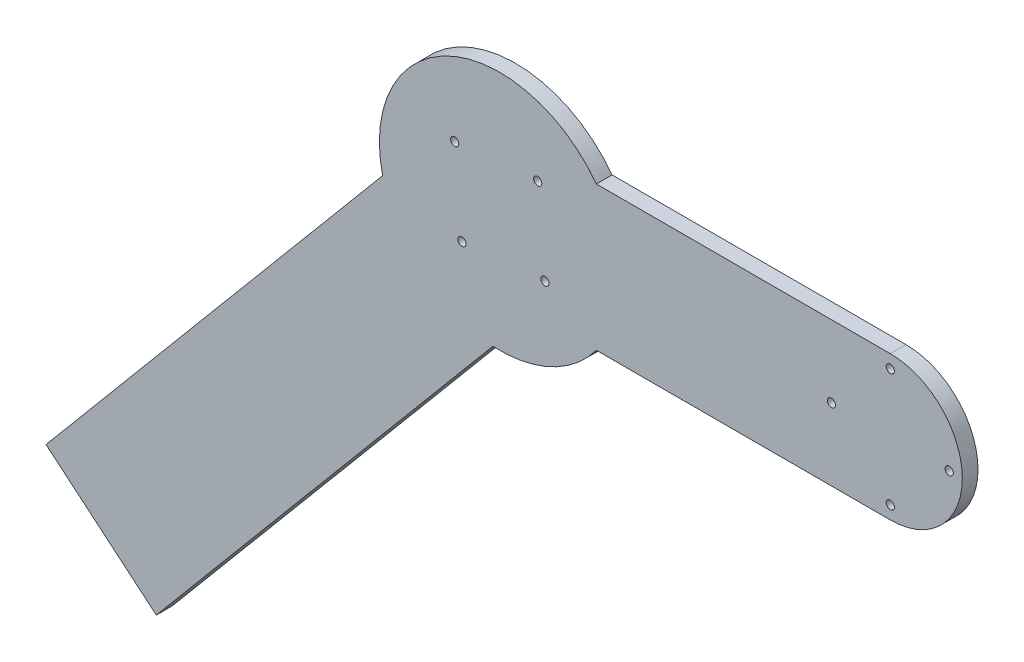
SolidWorks part; units mm, degrees
ref_plane "Front Plane" through (0, 0, 0) normal (0, 0, 1) x (1, 0, 0)
ref_plane "Top Plane" through (0, 0, 0) normal (0, 1, 0) x (1, 0, 0)
ref_plane "Right Plane" through (0, 0, 0) normal (1, 0, 0) x (0, 0, -1)
sketch "Sketch1" plane through (0, 0, 0) normal (0, 1, 0) x (1, 0, 0)
  line L0 (-47.5, -29.9135) -> (47.5, -29.9135) construction
  line L1 (-47.5, 56.6115) -> (47.5, 56.6115) construction
  line L2 (-47.5, 56.6115) -> (-47.5, -56.6115) construction
  line L3 (-47.5, -56.6115) -> (47.5, -56.6115) construction
  line L4 (47.5, 56.6115) -> (47.5, -56.6115) construction
  line L5 (-47.5, 56.6115) -> (47.5, -56.6115) construction
  line L6 (-47.5, -56.6115) -> (47.5, 56.6115) construction
  line L7 (-47.5, -23.9135) -> (47.5, -23.9135) construction
  line L8 (-47.5, 23.5865) -> (47.5, 23.5865) construction
  line L9 (47.5, 27.5865) -> (-47.5, 27.5865) construction
  line L10 (97.198, 47.5) -> (97.198, -47.5) construction
  line L11 (183.723, 47.5) -> (183.723, -47.5) construction
  line L12 (183.723, 47.5) -> (70.5, 47.5) construction
  line L13 (70.5, 47.5) -> (70.5, -47.5) construction
  line L14 (183.723, -47.5) -> (70.5, -47.5) construction
  line L15 (183.723, 47.5) -> (70.5, -47.5) construction
  line L16 (70.5, 47.5) -> (183.723, -47.5) construction
  line L17 (103.198, 47.5) -> (103.198, -47.5) construction
  line L18 (150.698, 47.5) -> (150.698, -47.5) construction
  line L19 (154.698, -47.5) -> (154.698, 47.5) construction
  line L20 (64.5, 88.7731) -> (64.5, -54.5) construction
  line L21 (47.5, -56.6115) -> (-248.4804, -56.6115) construction
  line L22 (47.5, -56.6115) -> (47.5, -62.6115) construction
  line L23 (47.5, -62.6115) -> (-248.4804, -62.6115) construction
  line L24 (-248.4804, -56.6115) -> (-248.4804, -62.6115) construction
  line L25 (64.5, -54.5) -> (327.1082, -54.5) construction
  line L26 (70.5, 94.7731) -> (70.5, -48.5) construction
  line L27 (70.5, -48.5) -> (327.1082, -48.5) construction
  line L28 (70.5, -48.5) -> (70.5, -54.5) construction
  line L29 (70.5, -48.5) -> (64.5, -48.5) construction
  line L30 (47.5, -56.6115) -> (47.5, -62.6115) construction
  line L31 (48.5, 17.5865) -> (48.5, -30) construction
  line L32 (48.5, -30) -> (54.5, -30) construction
  line L33 (54.5, -30) -> (54.5, 23.5865) construction
  line L34 (0, 0) -> (0, 56.6115) construction
  line L35 (-48.5, -30) -> (-54.5, -30) construction
  line L36 (-54.5, -30) -> (-54.5, 23.5865) construction
  line L37 (-48.5, 17.5865) -> (-48.5, -30) construction
  line L38 (54.5, 23.5865) -> (-54.5, 23.5865) construction
  line L39 (-48.5, 17.5865) -> (48.5, 17.5865) construction
  line L40 (48.5, 17.5865) -> (48.5, 23.5865) construction
  line L41 (70.5, 94.7731) -> (-59.952, 94.7731) construction
  line L42 (64.5, 88.7731) -> (-64.5, 88.7731) construction
  line L43 (-64.5, 88.7731) -> (-64.5, -48.5) construction
  line L44 (-64.5, -48.5) -> (-70.5, -48.5) construction
  line L45 (-70.5, -48.5) -> (-70.5, 98.5172) construction
  line L46 (-196.6321, -56.6115) -> (-196.6321, 23.9185) construction
  line L51 (-196.6321, -62.6115) -> (-101.6321, -62.6115) construction
  line L52 (-196.6321, -62.6115) -> (-196.6321, -89.3115) construction
  line L53 (-196.6321, -89.3115) -> (-101.6321, -89.3115) construction
  line L54 (-101.6321, -62.6115) -> (-101.6321, -89.3115) construction
  line L55 (-196.6321, 23.9185) -> (-101.6321, 23.9185) construction
  line L56 (-101.6321, 23.9185) -> (-101.6321, -56.6115) construction
  line L57 (-54.5, -23.9135) -> (-64.5, -23.9135) construction
  line L58 (54.5, -23.9135) -> (64.5, -23.9135) construction
  line L59 (64.5, 88.7731) -> (64.5, 94.7731) construction
  point P0 (0, 0)
  point P17 (127.1115, 0)
  point P67 (0, 0)
  point P68 (0, 0)
  dimension "D1" = 113.223
  dimension "D2" = 95
  dimension "D3" = 6
  dimension "D4" = 26.698
  dimension "D5" = 4
  dimension "D6" = 57.5
  dimension "D7" = 29.025
  dimension "D8" = 6
  dimension "D9" = 95
  dimension "D10" = 6
  dimension "D11" = 26.698
  dimension "D12" = 4
  dimension "D13" = 29.025
  dimension "D14" = 57.5
  dimension "D15" = 30
  dimension "D16" = 1
  dimension "D17" = 1
  dimension "D18" = 10
  dimension "D19" = 26.7
  dimension "D20" = 80.53
sketch "Sketch2" plane through (0, 0, 0) normal (0, 0, 1) x (1, 0, 0)
  line L0 (-47.5, 0) -> (47.5, 0) construction
  line L1 (-47.5, -50) -> (47.5, -50) construction
  line L2 (-47.5, -50) -> (-47.5, 50) construction
  line L3 (-47.5, 50) -> (47.5, 50) construction
  line L4 (47.5, -50) -> (47.5, 50) construction
  line L5 (-47.5, -50) -> (47.5, 50) construction
  line L6 (-47.5, 50) -> (47.5, -50) construction
  line L11 (0, 0) -> (0, 22.5) construction
  line L12 (-196.6321, 0) -> (-101.6321, 0) construction
  line L13 (-196.6321, 0) -> (-101.6321, 0) construction
  line L14 (0, 27.5) -> (-112.2573, 27.5)
  line L16 (-112.2573, -27.5) -> (0, -27.5)
  line L17 (-151.7685, -45.9244) -> (-280.326, -199.1333)
  line L18 (-193.9009, -10.5711) -> (-322.4585, -163.78)
  line L19 (-112.2573, -27.5) -> (-112.2573, 27.5) construction
  line L20 (-151.7685, -45.9244) -> (-193.9009, -10.5711) construction
  line L21 (-172.8347, -28.2477) -> (-301.3922, -181.4566) construction
  line L22 (-280.326, -199.1333) -> (-322.4585, -163.78)
  circle A0 centre (0, 0) radius 22.5 construction
  circle A1 centre (0, 22.5) radius 1.5635
  circle A2 centre (22.5, 0) radius 1.5635
  circle A3 centre (0, -22.5) radius 1.5635
  circle A4 centre (-22.5, 0) radius 1.5635
  circle A5 centre (-171.6321, 0) radius 1.5635 construction
  circle A6 centre (-149.1321, 0) radius 22.5 construction
  circle A7 centre (-149.1321, 22.5) radius 1.5635 construction
  circle A8 centre (-126.6321, 0) radius 1.5635 construction
  circle A9 centre (-149.1321, -22.5) radius 1.5635 construction
  arc A10 (0, 27.5) -> (0, -27.5) centre (0, 0) cw
  arc A11 (-112.2573, 27.5) -> (-193.9009, -10.5711) centre (-149.1321, 0) ccw
  arc A12 (-112.2573, -27.5) -> (-151.7685, -45.9244) centre (-149.1321, 0) cw
  circle A13 centre (-131.8961, -14.4627) radius 1.5635
  circle A14 centre (-163.5948, -17.236) radius 1.5635
  circle A15 centre (-166.3681, 14.4627) radius 1.5635
  circle A16 centre (-134.6693, 17.236) radius 1.5635
  point P0 (0, 0)
  point P15 (0, 0)
  point P18 (0, 0)
  point P21 (0, 0)
  point P24 (0, 0)
  point P39 (-47.5, 51)
  point P40 (-47.5, -51)
  point P45 (39.0018, -114.5245)
  point P47 (-149.1321, 0)
  point P48 (0, 0)
  point P57 (-149.1321, 0)
  dimension "D3" = 45
  dimension "D4" = 3.127
  dimension "D7" = 5
  dimension "D8" = 46
  dimension "D1" = 100
  dimension "D2" = 95
  dimension "D9" = 1
  dimension "D10" = 130
  dimension "D11" = 200
  dimension "D6" = 2
  dimension "D5" = 4
  dimension "D12" = 4
extrude "Boss-Extrude1" add sketch "Sketch2" along normal up to vertex (62.6115 mm away) from vertex up to point (47.5, 0, 62.6115) starting at point (47.5, 0, 56.6115)
sketch "Sketch3" [suppressed] plane through (0, 0, 0) normal (0, 1, 0) x (1, 0, 0)
  line L0 (-48.5, -30) -> (-54.5, -30) construction
  line L1 (-48.5, 17.5865) -> (-48.5, -30) construction
  line L2 (-54.5, -30) -> (-54.5, 23.5865) construction
  line L3 (-48.5, 17.5865) -> (48.5, 17.5865) construction
  line L4 (54.5, 23.5865) -> (-54.5, 23.5865) construction
  line L5 (54.5, -30) -> (54.5, 23.5865) construction
  line L6 (48.5, 17.5865) -> (48.5, -30) construction
  line L7 (48.5, -30) -> (54.5, -30) construction
  line L8 (-48.5, -30) -> (-54.5, -30)
  line L9 (-48.5, 17.5865) -> (-48.5, -30)
  line L10 (-54.5, -30) -> (-54.5, 23.5865)
  line L11 (-48.5, 17.5865) -> (48.5, 17.5865)
  line L12 (54.5, 23.5865) -> (-54.5, 23.5865)
  line L13 (54.5, -30) -> (54.5, 23.5865)
  line L14 (48.5, 17.5865) -> (48.5, -30)
  line L15 (48.5, -30) -> (54.5, -30)
extrude "Boss-Extrude2" [suppressed] add sketch "Sketch3" along normal up to vertex and the other way up to vertex up to point (-47.5, 51, 0) other way up to point (-47.5, -51, 0)
sketch "Sketch4" [suppressed] plane through (0, 0, -17.5865) normal (0, 0, 1) x (1, 0, 0)
  line L1 (30, -45) -> (-30, -45) construction
  line L2 (30, -45) -> (30, 45) construction
  line L3 (30, 45) -> (-30, 45) construction
  line L4 (-30, -45) -> (-30, 45) construction
  line L5 (30, -45) -> (-30, 45) construction
  line L6 (30, 45) -> (-30, -45) construction
  circle A0 centre (0, 0) radius 46.25
  circle A1 centre (-30, 45) radius 2.25
  circle A2 centre (30, 45) radius 2.25
  circle A3 centre (30, -45) radius 2.25
  circle A4 centre (-30, -45) radius 2.25
  dimension "D1" = 92.5
  dimension "D4" = 4.5
  dimension "D2" = 90
  dimension "D3" = 60
extrude "Cut-Extrude1" [suppressed] cut sketch "Sketch4" against normal through all
sketch "Sketch5" [suppressed] plane through (54.5, 0, 0) normal (1, 0, 0) x (0, 0, -1)
  circle A0 centre (0, 0) radius 14.2875
  point P0 (0, 0)
  dimension "D1" = 28.575
extrude "Cut-Extrude2" [suppressed] cut sketch "Sketch5" against normal through all
